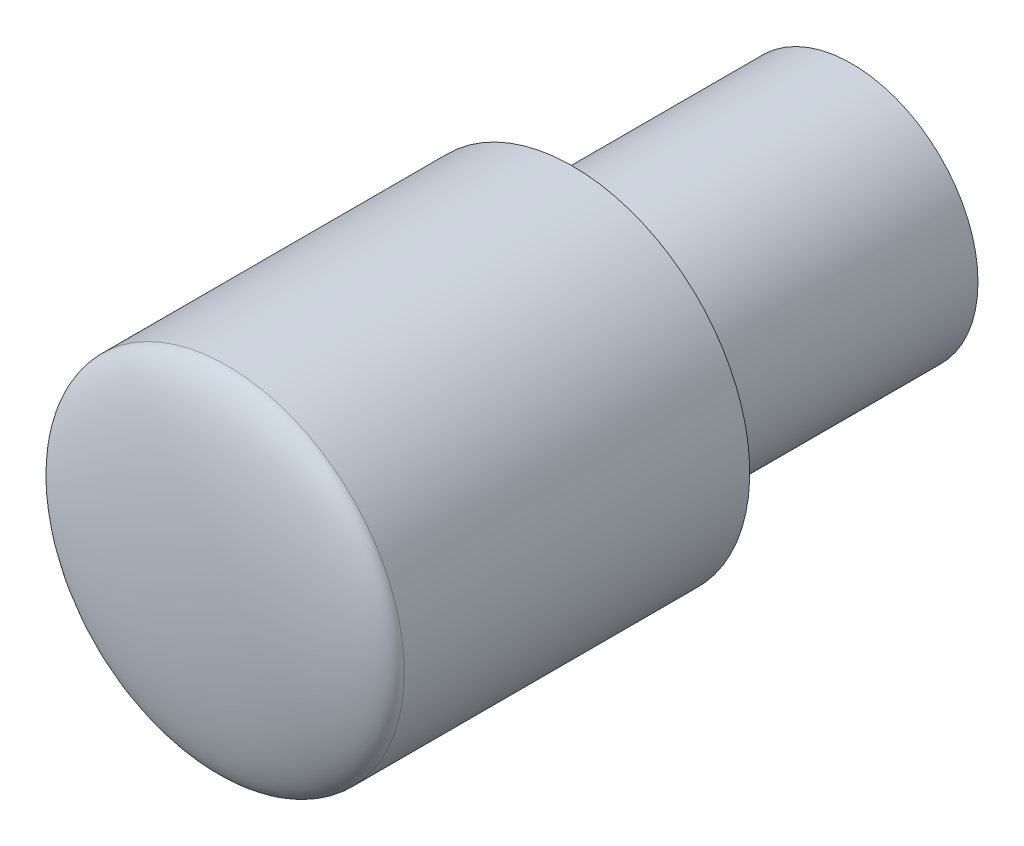
SolidWorks part; units mm, degrees
ref_plane "Front" through (0, 0, 0) normal (0, 0, 1) x (1, 0, 0)
ref_plane "Top" through (0, 0, 0) normal (0, 1, 0) x (1, 0, 0)
ref_plane "Right" through (0, 0, 0) normal (1, 0, 0) x (0, 0, -1)
sketch "Sketch1" plane through (0, 0, 0) normal (0, 0, 1) x (1, 0, 0)
  circle A0 centre (-45.925, 18.948) radius 11.4341
extrude "Base-Extrude" add sketch "Sketch1" along normal blind 40.3601
dome "Dome1" faces to dome 1 distance 2.54 reverse direction no elliptical dome yes face at (-34.4909, 18.948, 40.3601) parameters "D1"=2.54
sketch "Sketch2" plane through (0, 0, 0) normal (0, 0, -1) x (-1, 0, 0)
  circle A0 centre (45.925, 18.948) radius 8.1494
extrude "Cut-Extrude1" cut sketch "Sketch2" against normal blind 18.034 flip side to cut
